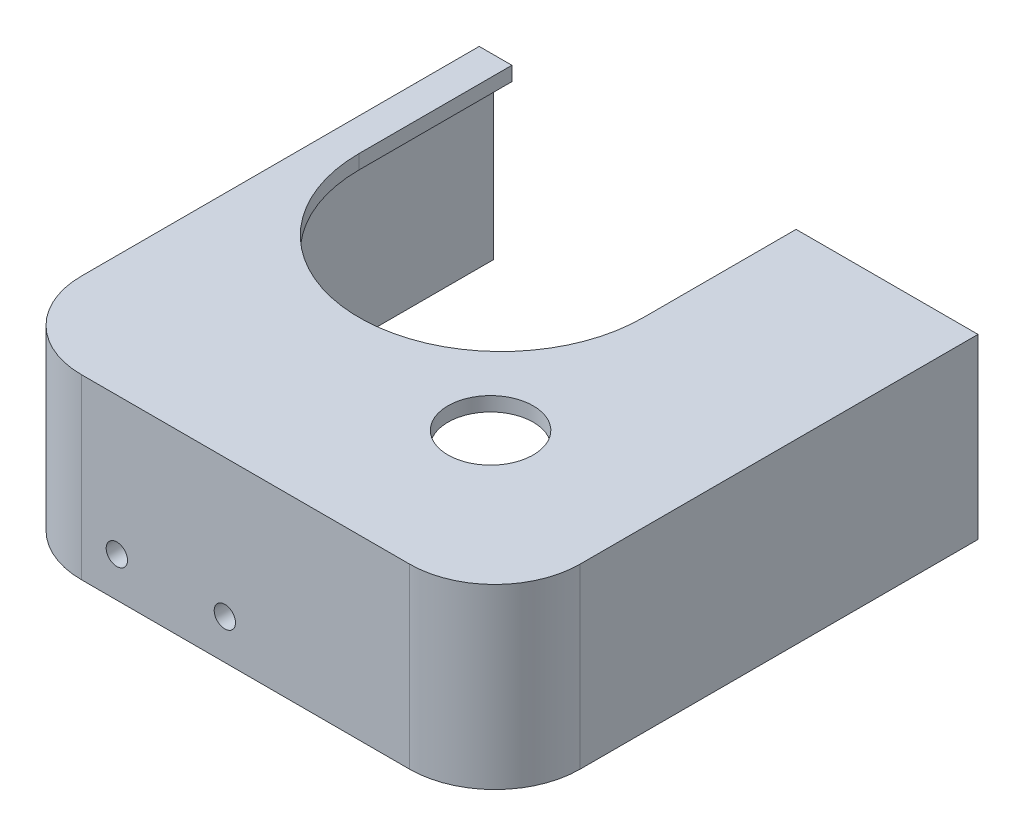
SolidWorks part; units mm, degrees
ref_plane "Front Plane" through (0, 0, 0) normal (0, 0, 1) x (1, 0, 0)
ref_plane "Top Plane" through (0, 0, 0) normal (0, 1, 0) x (1, 0, 0)
ref_plane "Right Plane" through (0, 0, 0) normal (1, 0, 0) x (0, 0, -1)
sketch "Sketch1" plane through (0, 0, 0) normal (0, 0, 1) x (1, 0, 0)
  line L0 (-9.8995, -2) -> (-9.8995, -8) construction
  line L1 (-9.8995, -8) -> (-5.5, -8) construction
  line L2 (-5.5, -8) -> (-5.5, -2) construction
  line L3 (-5.5, -2) -> (-9.8995, -2) construction
  line L4 (-17.5, -2) -> (-17.5, -8) construction
  line L5 (-17.5, -8) -> (-13.1005, -8) construction
  line L6 (-13.1005, -8) -> (-13.1005, -2) construction
  line L7 (-13.1005, -2) -> (-17.5, -2) construction
  line L8 (-9.8995, -2) -> (-9.8995, -8)
  line L9 (-9.8995, -8) -> (-5.5, -8)
  line L10 (-5.5, -8) -> (-5.5, -2)
  line L11 (-5.5, -2) -> (-9.8995, -2)
  line L12 (-17.5, -2) -> (-17.5, -8)
  line L13 (-17.5, -8) -> (-13.1005, -8)
  line L14 (-13.1005, -8) -> (-13.1005, -2)
  line L15 (-13.1005, -2) -> (-17.5, -2)
  circle A0 centre (-7.7, -4.8) radius 0.75 construction
  circle A1 centre (-15.3, -4.8) radius 0.75 construction
  circle A2 centre (-7.7, -4.8) radius 0.75
  circle A3 centre (-15.3, -4.8) radius 0.75
extrude "Boss-Extrude1" add sketch "Sketch1" along normal blind 1.5
sketch "Sketch2" plane through (0, 0, 1.5) normal (0, 0, 1) x (1, 0, 0)
  line L0 (-22.8, -2) -> (-22.8, -14.5)
  line L1 (13, -2) -> (-24.5, -2) construction
  line L2 (-22.8, -14.5) -> (11.3, -14.5)
  line L3 (11.3, -14.5) -> (11.3, -2)
  line L4 (11.3, -2) -> (-22.8, -2)
  circle A0 centre (-7.7, -4.8) radius 0.75 construction
  circle A1 centre (-15.3, -4.8) radius 0.75 construction
  circle A2 centre (-7.7, -4.8) radius 0.75
  circle A3 centre (-15.3, -4.8) radius 0.75
  dimension "D1" = 7.5
  dimension "D2" = 19
  dimension "D3" = 12.5
extrude "Boss-Extrude2" add sketch "Sketch2" against normal blind 1
sketch "Sketch4" plane through (0, -14.5, 0) normal (0, -1, 0) x (1, 0, 0)
  line L0 (-22.8, 0.5) -> (-22.8, -32.5)
  line L1 (-22.8, -32.5) -> (-21.5, -32.5)
  line L2 (11.3, -32.5) -> (11.3, 0.5)
  line L3 (11.3, 0.5) -> (-22.8, 0.5)
  line L4 (-21.5, -21.75) -> (-21.5, -32.5)
  line L5 (-1.5, -21.75) -> (-1.5, -32.5)
  line L6 (-1.5, -32.5) -> (11.3, -32.5)
  arc A0 (-1.5, -21.75) -> (-21.5, -21.75) centre (-11.5, -21.75) ccw
  circle A1 centre (-11.5, -21.75) radius 4 construction
  dimension "D1" = 10
  dimension "D2" = 33
extrude "Boss-Extrude3" add sketch "Sketch4" against normal blind 1
sketch "Sketch5" plane through (-22.8, 0, 0) normal (-1, 0, 0) x (0, 0, 1)
  line L0 (1.5, -2) -> (1.5, -14.5)
  line L1 (1.5, -14.5) -> (-32.5, -14.5)
  line L2 (-32.5, -14.5) -> (-32.5, -2)
  line L3 (0.375, -2) -> (-31.625, -2) construction
  line L4 (-32.5, -2) -> (1.5, -2)
extrude "Boss-Extrude4" add sketch "Sketch5" along normal blind 1
sketch "Sketch6" plane through (11.3, 0, 0) normal (1, 0, 0) x (0, 0, -1)
  line L1 (-1.5, -2) -> (32.5, -2)
  line L2 (31.625, -2) -> (-0.375, -2) construction
  line L3 (32.5, -2) -> (32.5, -13.5) construction
  line L4 (32.5, -2) -> (32.5, -14.5)
  line L6 (-1.5, -2) -> (-1.5, -14.5)
  line L7 (-1.5, -14.5) -> (32.5, -14.5)
  line L8 (32.5, -14.5) -> (32.5, -13.5)
  line L9 (32.5, -13.5) -> (-0.5, -13.5)
  line L10 (-0.5, -13.5) -> (-0.5, -2)
  line L11 (-0.5, -2) -> (-1.5, -2)
  line L12 (-1.5, -2) -> (-1.5, -14.5)
  line L13 (-1.5, -14.5) -> (32.5, -14.5)
  dimension "D1" = 0
extrude "Boss-Extrude5" add sketch "Sketch6" against normal blind 1
sketch "Sketch7" plane through (0, 0, 0.5) normal (0, 0, -1) x (-1, 0, 0)
  line L0 (9.8995, -2) -> (9.8995, -8)
  line L1 (9.8995, -8) -> (13.1005, -8)
  line L2 (13.1005, -8) -> (13.1005, -2)
  line L3 (13.1005, -2) -> (17.5, -2) construction
  line L4 (13.1005, -8) -> (13.1005, -2) construction
  line L5 (13.1005, -2) -> (9.8995, -2)
extrude "Boss-Extrude6" add sketch "Sketch7" along normal blind 2
fillet "Fillet1" radius 2 1 edges at (-11.5, -8, 0.5)
fillet "Fillet2" radius 5 1 edges at (-22.8, -7.75, 0.5)
fillet "Fillet3" radius 6 1 edges at (-23.8, -8.25, 1.5)
fillet "Fillet4" radius 5 1 edges at (10.3, -7.75, 0.5)
fillet "Fillet5" radius 6 1 edges at (11.3, -8.25, 1.5)
sketch "Sketch8" plane through (0, -13.5, 0) normal (0, 1, 0) x (1, 0, 0)
  circle A0 centre (0, 9.5) radius 3
  dimension "D1" = 6
extrude "Cut-Extrude1" cut sketch "Sketch8" against normal blind 2
mirror "Mirror1" about plane through (-11.5, -13.5, -21.75) normal (0, -1, 0) of "Cut-Extrude1", "Fillet5", "Fillet4", "Fillet3", "Fillet2", "Fillet1", "Boss-Extrude6", "Boss-Extrude5", "Boss-Extrude4", "Boss-Extrude3", "Boss-Extrude2", "Boss-Extrude1"
sketch "Sketch9" plane through (0, -2, 0) normal (0, 1, 0) x (1, 0, 0)
  line L16 (-17.8, -1.5) -> (5.3, -1.5)
  line L17 (11.3, 4.5) -> (11.3, 32.5)
  line L18 (11.3, 32.5) -> (10.3, 32.5)
  line L19 (10.3, 32.5) -> (10.3, 4.5)
  line L20 (5.3, -0.5) -> (-5.5, -0.5)
  line L21 (-5.5, -0.5) -> (-5.5, 0)
  line L22 (-5.5, 0) -> (-9.8995, 0)
  line L23 (-9.8995, 0) -> (-9.8995, 1.5)
  line L24 (-9.8995, 1.5) -> (-13.1005, 1.5)
  line L25 (-13.1005, 1.5) -> (-13.1005, 0)
  line L26 (-13.1005, 0) -> (-17.5, 0)
  line L27 (-17.5, 0) -> (-17.5, -0.5)
  line L28 (-17.5, -0.5) -> (-17.8, -0.5)
  line L29 (-22.8, 4.5) -> (-22.8, 32.5)
  line L30 (-22.8, 32.5) -> (-23.8, 32.5)
  line L31 (-23.8, 32.5) -> (-23.8, 4.5)
  line L32 (-17.8, -1.5) -> (5.3, -1.5)
  line L33 (11.3, 4.5) -> (11.3, 32.5)
  line L34 (11.3, 32.5) -> (10.3, 32.5)
  line L35 (10.3, 32.5) -> (10.3, 4.5)
  line L36 (5.3, -0.5) -> (-5.5, -0.5)
  line L37 (-5.5, -0.5) -> (-5.5, 0)
  line L38 (-5.5, 0) -> (-9.8995, 0)
  line L39 (-9.8995, 0) -> (-9.8995, 1.5)
  line L40 (-9.8995, 1.5) -> (-13.1005, 1.5)
  line L41 (-13.1005, 1.5) -> (-13.1005, 0)
  line L42 (-13.1005, 0) -> (-17.5, 0)
  line L43 (-17.5, 0) -> (-17.5, -0.5)
  line L44 (-17.5, -0.5) -> (-17.8, -0.5)
  line L45 (-22.8, 4.5) -> (-22.8, 32.5)
  line L46 (-22.8, 32.5) -> (-23.8, 32.5)
  line L47 (-23.8, 32.5) -> (-23.8, 4.5)
  arc A4 (5.3, -1.5) -> (11.3, 4.5) centre (5.3, 4.5) ccw
  arc A5 (5.3, -0.5) -> (10.3, 4.5) centre (5.3, 4.5) ccw
  arc A6 (-22.8, 4.5) -> (-17.8, -0.5) centre (-17.8, 4.5) ccw
  arc A7 (-23.8, 4.5) -> (-17.8, -1.5) centre (-17.8, 4.5) ccw
  arc A8 (5.3, -1.5) -> (11.3, 4.5) centre (5.3, 4.5) ccw
  arc A9 (5.3, -0.5) -> (10.3, 4.5) centre (5.3, 4.5) ccw
  arc A10 (-22.8, 4.5) -> (-17.8, -0.5) centre (-17.8, 4.5) ccw
  arc A11 (-23.8, 4.5) -> (-17.8, -1.5) centre (-17.8, 4.5) ccw
  dimension "D1" = 0
extrude "Cut-Extrude2" cut sketch "Sketch9" against normal blind 10.5
sketch "Sketch10" plane through (0, -12.5, 0) normal (0, 1, 0) x (1, 0, 0)
  line L7 (-23.8, 32.5) -> (-23.8, 4.5)
  line L13 (-23.8, 32.5) -> (-23.8, 4.5)
  line L15 (-17.8, -1.5) -> (5.3, -1.5)
  line L17 (-17.8, -1.5) -> (5.3, -1.5)
  line L18 (11.3, 4.5) -> (11.3, 32.5)
  line L19 (11.3, 4.5) -> (11.3, 32.5)
  line L24 (11.3, 32.5) -> (-1.5, 32.5)
  line L25 (-1.5, 32.5) -> (-1.5, 21.75)
  line L26 (-21.5, 21.75) -> (-21.5, 32.5)
  line L27 (-21.5, 32.5) -> (-23.8, 32.5)
  line L39 (11.3, 32.5) -> (-1.5, 32.5)
  line L40 (-1.5, 32.5) -> (-1.5, 21.75)
  line L41 (-21.5, 21.75) -> (-21.5, 32.5)
  line L42 (-21.5, 32.5) -> (-23.8, 32.5)
  arc A3 (-23.8, 4.5) -> (-17.8, -1.5) centre (-17.8, 4.5) ccw
  arc A4 (-21.5, 21.75) -> (-1.5, 21.75) centre (-11.5, 21.75) ccw
  arc A7 (-21.5, 21.75) -> (-1.5, 21.75) centre (-11.5, 21.75) ccw
  arc A13 (-23.8, 4.5) -> (-17.8, -1.5) centre (-17.8, 4.5) ccw
  arc A15 (5.3, -1.5) -> (11.3, 4.5) centre (5.3, 4.5) ccw
  arc A16 (5.3, -1.5) -> (11.3, 4.5) centre (5.3, 4.5) ccw
  dimension "D1" = 0
extrude "Cut-Extrude3" [suppressed] cut sketch "Sketch10" against normal blind 1
sketch "Sketch12" plane through (0, -14.5, 0) normal (0, -1, 0) x (1, 0, 0)
  line L7 (-22.8, -4.5) -> (-22.8, -32.5)
  line L8 (-22.8, -32.5) -> (-21.5, -32.5)
  line L9 (-21.5, -32.5) -> (-21.5, -21.75)
  line L10 (-1.5, -21.75) -> (-1.5, -32.5)
  line L11 (-1.5, -32.5) -> (10.3, -32.5)
  line L12 (10.3, -32.5) -> (10.3, -4.5)
  line L13 (5.3, 0.5) -> (-17.8, 0.5)
  line L14 (-22.8, -4.5) -> (-22.8, -32.5)
  line L15 (-22.8, -32.5) -> (-21.5, -32.5)
  line L16 (-21.5, -32.5) -> (-21.5, -21.75)
  line L17 (-1.5, -21.75) -> (-1.5, -32.5)
  line L18 (-1.5, -32.5) -> (10.3, -32.5)
  line L19 (10.3, -32.5) -> (10.3, -4.5)
  line L20 (5.3, 0.5) -> (-17.8, 0.5)
  arc A3 (-1.5, -21.75) -> (-21.5, -21.75) centre (-11.5, -21.75) ccw
  arc A4 (10.3, -4.5) -> (5.3, 0.5) centre (5.3, -4.5) ccw
  arc A5 (-17.8, 0.5) -> (-22.8, -4.5) centre (-17.8, -4.5) ccw
  arc A6 (-1.5, -21.75) -> (-21.5, -21.75) centre (-11.5, -21.75) ccw
  arc A7 (10.3, -4.5) -> (5.3, 0.5) centre (5.3, -4.5) ccw
  arc A8 (-17.8, 0.5) -> (-22.8, -4.5) centre (-17.8, -4.5) ccw
  dimension "D1" = 0
extrude "Cut-Extrude4" cut sketch "Sketch12" against normal blind 1
